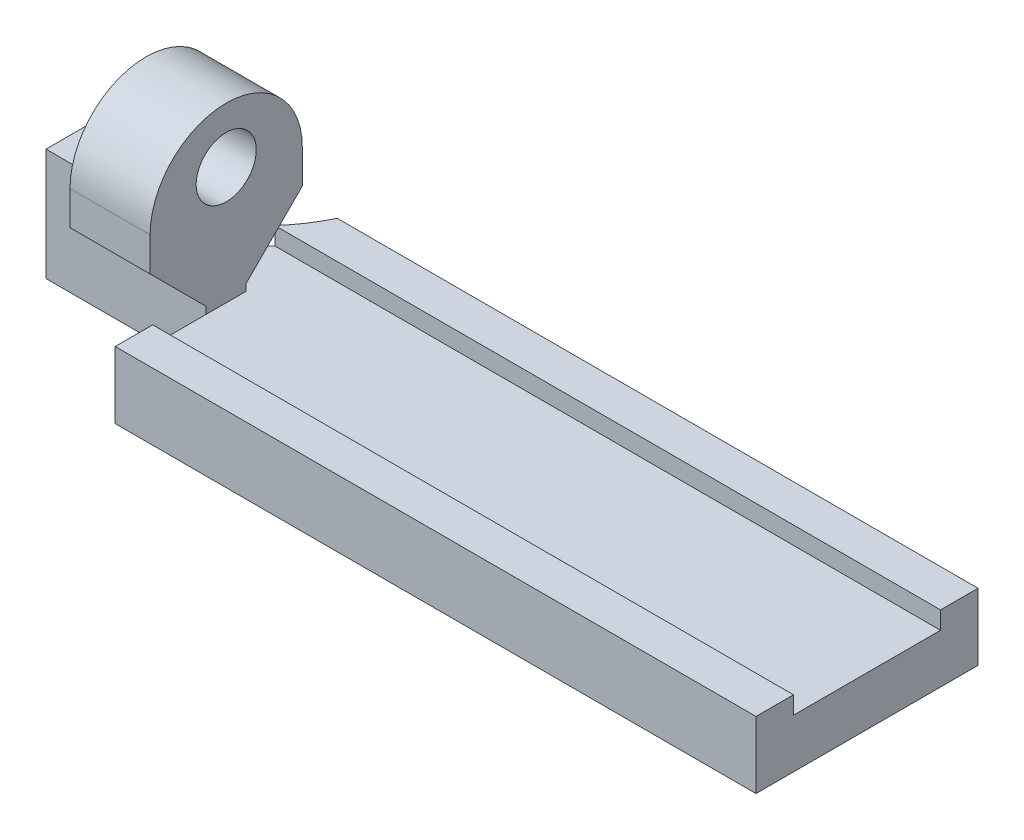
SolidWorks part; units mm, degrees
ref_plane "Front Plane" through (0, 0, 0) normal (0, 0, 1) x (1, 0, 0)
ref_plane "Top Plane" through (0, 0, 0) normal (0, 1, 0) x (1, 0, 0)
ref_plane "Right Plane" through (0, 0, 0) normal (1, 0, 0) x (0, 0, -1)
sketch "Sketch1" plane through (0, 0, 0) normal (0, 0, 1) x (1, 0, 0)
  line L0 (0, 0) -> (-12.7, 0)
  line L1 (-12.7, 0) -> (-12.7, 8.89)
  line L2 (-12.7, 8.89) -> (0, 8.89)
  line L3 (0, 8.89) -> (0, 0)
  dimension "D1" = 12.7
  dimension "D2" = 8.89
extrude "Boss-Extrude1" add sketch "Sketch1" along normal blind 3.175
sketch "Sketch2" plane through (0, 0, 0) normal (1, 0, 0) x (0, 0, -1)
  line L3 (-3.175, 4.445) -> (-7.62, 8.89)
  line L8 (-3.175, 0) -> (-3.175, 8.89) construction
  line L9 (-7.62, 8.89) -> (-7.62, 11.5786)
  line L10 (0, 0) -> (0, 8.89) construction
  line L11 (0, 4.445) -> (4.445, 8.89)
  line L12 (4.445, 8.89) -> (4.445, 11.5786)
  line L13 (-3.175, 8.89) -> (0, 8.89) construction
  line L14 (-3.175, 8.89) -> (0, 8.89)
  line L15 (0, 4.445) -> (0, 8.89)
  line L16 (-3.175, 4.445) -> (-3.175, 8.89)
  line L17 (-3.175, 0) -> (0, 0) construction
  arc A4 (-7.62, 11.5786) -> (4.445, 11.5786) centre (-1.5875, 11.5786) cw
  circle A5 centre (-1.5875, 13.208) radius 2.3813
  dimension "D1" = 12.065
  dimension "D8" = 4.7625
  dimension "D2" = 45
  dimension "D3" = 45
  dimension "D4" = 2.6886
  dimension "D5" = 2.6886
  dimension "D6" = 4.318
  dimension "D7" = 1.5875
extrude "Boss-Extrude2" add sketch "Sketch2" against normal blind 6.35
ref_plane "Plane1" through (0, 0, 3.175) normal (1, 0, 0) x (0, 0, -1)
sketch "Sketch4" plane through (0, 8.89, 0) normal (0, 1, 0) x (1, 0, 0)
  line L0 (-12.7, -3.175) -> (-12.7, 0) construction
  circle A0 centre (-7.62, -1.5875) radius 1.1906
  dimension "D1" = 2.3813
  dimension "D2" = 5.08
extrude "Cut-Extrude1" cut sketch "Sketch4" against normal up to next
sketch "Sketch5" plane through (0, 0, 0) normal (1, 0, 0) x (0, 0, -1)
  line L0 (-7.4168, 5.2968) -> (-10.3875, 5.2968)
  line L1 (-10.3875, 5.2968) -> (-10.3875, 0)
  line L2 (-10.3875, 0) -> (0, 0)
  line L4 (0, 0) -> (0, 4.445) construction
  line L5 (0, 3.8956) -> (-3.175, 3.8956)
  line L6 (-3.175, 0) -> (-3.175, 4.445) construction
  line L7 (-3.175, 3.8956) -> (-7.4168, 3.8956)
  line L8 (-7.4168, 3.8956) -> (-7.4168, 5.2968)
  line L9 (-3.175, 0) -> (0, 0) construction
  line L10 (-1.5875, 3.8956) -> (-1.5875, 0) construction
  line L11 (0, 3.8956) -> (4.2418, 3.8956)
  line L12 (7.2125, 5.2968) -> (7.2125, 0)
  line L13 (4.2418, 3.8956) -> (4.2418, 5.2968)
  line L14 (4.2418, 5.2968) -> (7.2125, 5.2968)
  line L15 (7.2125, 0) -> (0, 0)
  dimension "D1" = 5.2968
  dimension "D2" = 2.9707
  dimension "D3" = 3.8956
  dimension "D4" = 4.2418
extrude "Boss-Extrude3" add sketch "Sketch5" along normal blind 50.8
fillet "Fillet1" radius 12.7 1 edges at (0, 1.9478, 0)
sketch "Sketch8" plane through (-12.7, 0, 0) normal (-1, 0, 0) x (0, 0, 1)
  line L0 (1.5875, 8.89) -> (1.5875, 0) construction
  line L1 (3.175, 8.89) -> (0, 8.89) construction
  line L2 (3.175, 0) -> (0, 0) construction
ref_plane "Plane2" through (0, 0, 1.5875) normal (0, 0, 1) x (0, -1, 0)
